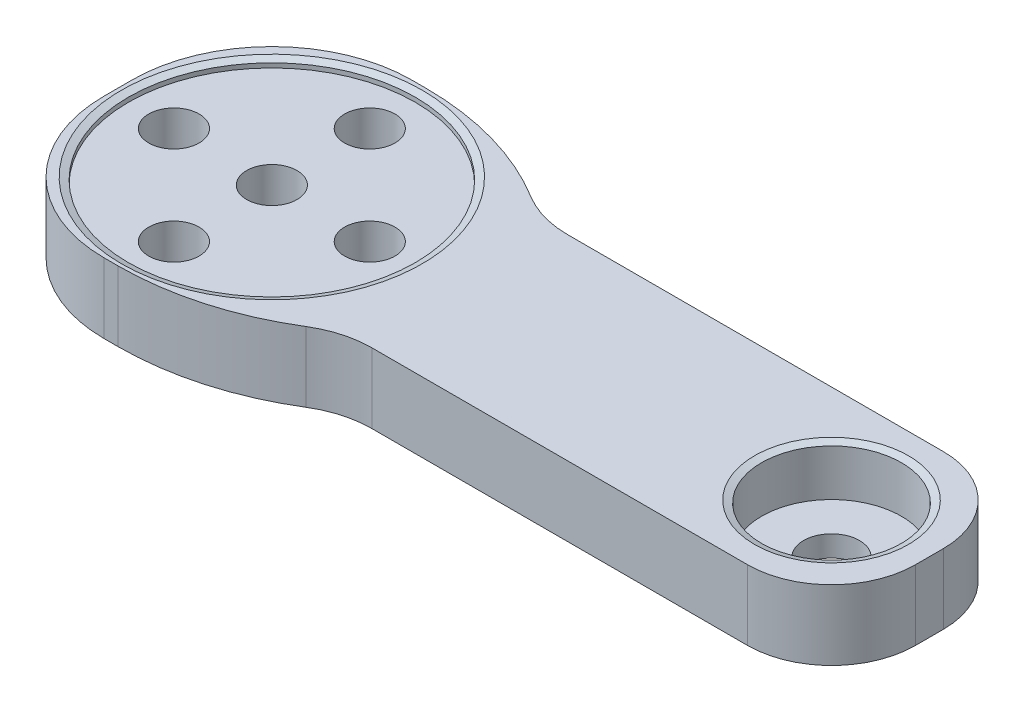
SolidWorks part; units mm, degrees
ref_plane "Спереди" through (0, 0, 0) normal (0, 0, 1) x (1, 0, 0)
ref_plane "Сверху" through (0, 0, 0) normal (0, 1, 0) x (1, 0, 0)
ref_plane "Справа" through (0, 0, 0) normal (1, 0, 0) x (0, 0, -1)
sketch "Эскиз2" plane through (0, 0, 0) normal (0, 1, 0) x (1, 0, 0)
  line L1 (-29, -11) -> (29, -11)
  line L2 (-29, -11) -> (-29, 11)
  line L3 (-29, 11) -> (29, 11)
  line L4 (29, -11) -> (29, 11)
  line L5 (-29, -11) -> (29, 11) construction
  line L6 (-29, 11) -> (29, -11) construction
  point P0 (0, 0)
  dimension "D1" = 58
  dimension "D2" = 22
extrude "Бобышка-Вытянуть1" add sketch "Эскиз2" along normal blind 5
sketch "Эскиз4" plane through (0, 5, 0) normal (0, 1, 0) x (1, 0, 0)
  line L0 (-18, 11) -> (-18, -11) construction
  line L3 (-43.8194, 0) -> (-21.4047, 0) construction
  line L4 (-29, 11) -> (-29, -11) construction
  circle A0 centre (-18, 0) radius 10.25
  circle A1 centre (-18, 0) radius 7 construction
  circle A2 centre (-18, 7) radius 1.8
  circle A3 centre (-18, -7) radius 1.8
  circle A4 centre (-25, 0) radius 1.8
  circle A5 centre (-11, 0) radius 1.8
  circle A6 centre (-18, 0) radius 1.8
  dimension "D1" = 20.5
  dimension "D2" = 14
  dimension "D3" = 3.6
  dimension "D4" = 11
extrude "Вырез-Вытянуть1" cut sketch "Эскиз4" against normal blind 0.5 contours A5 A0 A4 A3 A2 region at (-27.9601, 5, 0)
extrude "Вырез-Вытянуть2" cut sketch "Эскиз4<3>" against normal blind 10 contours A2 | A5 | A3 | A4 | A6 region at (-18, 5, -7) region at (-18, 5, 7) region at (-25, 5, 0) region at (-11, 5, 0) region at (-18, 5, 0)
sketch "Эскиз4<3>" plane through (0, 5, 0) normal (0, 1, 0) x (1, 0, 0) same geometry as "Эскиз4"
sketch "Эскиз5" plane through (0, 5, 0) normal (0, 1, 0) x (1, 0, 0)
  line L1 (29, 11) -> (-6, 11)
  line L2 (29, 11) -> (29, 7)
  line L3 (29, 7) -> (-6, 7)
  line L4 (-6, 11) -> (-6, 7)
  line L5 (40.1314, 0) -> (-44.1872, 0) construction
  line L6 (29, -7) -> (-6, -7)
  line L7 (-6, -11) -> (-6, -7)
  line L8 (29, -11) -> (-6, -11)
  line L9 (29, -11) -> (29, -7)
  dimension "D1" = 4
  dimension "D2" = 35
extrude "Вырез-Вытянуть3" cut sketch "Эскиз5" against normal blind 10
sketch "Эскиз6" plane through (0, 5, 0) normal (0, 1, 0) x (1, 0, 0)
  line L0 (29, -7) -> (29, 7) construction
  circle A0 centre (22, 0) radius 5
  dimension "D1" = 10
  dimension "D2" = 7
extrude "Вырез-Вытянуть4" cut sketch "Эскиз6" against normal blind 3.5
chamfer "Фаска1" distance 0.5 angle 20 2 edges at (22, 5, 5) (-18, 5, 10.25) first distance on face at (22, 5, 5)
sketch "Эскиз7" plane through (0, 1.5, 0) normal (0, 1, 0) x (1, 0, 0)
  circle A0 centre (22, 0) radius 2
extrude "Вырез-Вытянуть5" cut sketch "Эскиз7" against normal blind 3.5
fillet "Скругление2" radius 10 2 edges at (-29, 2.5, -11) (-29, 2.5, 11)
fillet "Скругление3" radius 6 2 edges at (29, 2.5, -7) (29, 2.5, 7)
fillet "Скругление4" radius 20 2 edges at (-6, 2.5, -11) (-6, 2.5, 11)
fillet "Скругление5" radius 7 2 edges at (-6, 2.5, 7) (-6, 2.5, -7)
